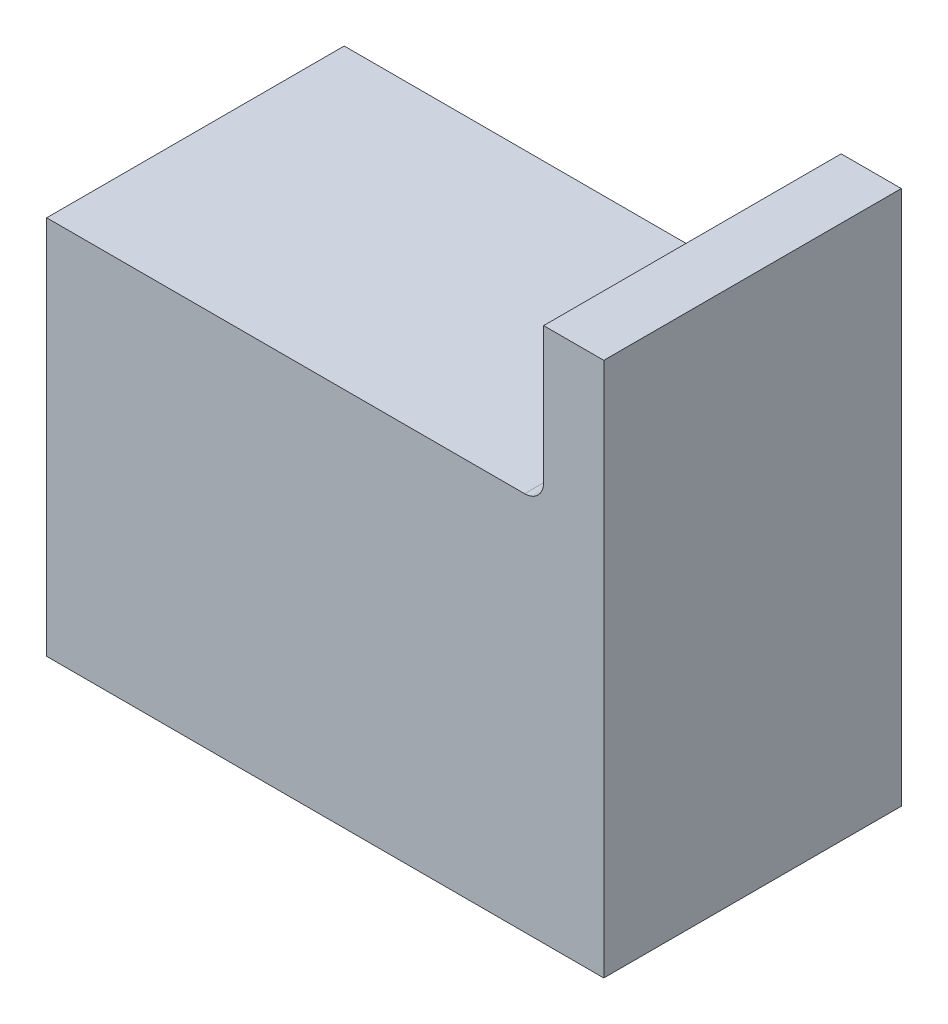
SolidWorks part; units mm, degrees
ref_plane "Front Plane" through (0, 0, 0) normal (0, 0, 1) x (1, 0, 0)
ref_plane "Top Plane" through (0, 0, 0) normal (0, 1, 0) x (1, 0, 0)
ref_plane "Right Plane" through (0, 0, 0) normal (1, 0, 0) x (0, 0, -1)
sketch "Sketch1" plane through (0, 0, 0) normal (0, 1, 0) x (1, 0, 0)
  line L1 (-44, 23.5) -> (44, 23.5)
  line L2 (-44, 23.5) -> (-44, -23.5)
  line L3 (-44, -23.5) -> (44, -23.5)
  line L4 (44, 23.5) -> (44, -23.5)
  line L5 (0, -23.5) -> (0, 23.5) construction
  line L6 (-44, 0) -> (44, 0) construction
  circle A0 centre (25.5, 18) radius 2.5
  circle A2 centre (25.5, -18) radius 2.5
  point P0 (0, 0)
  dimension "D3" = 5
  dimension "D4" = 5.5
  dimension "D1" = 47
  dimension "D2" = 88
  dimension "D5" = 18.5
extrude "Boss-Extrude1" add sketch "Sketch1" along normal blind 60
extrude "Boss-Extrude2" add sketch "Sketch1<2>" along normal blind 40 from offset 20 contours A2 | A0 region at (25.5, 0, -18) region at (25.5, 0, 18)
sketch "Sketch1<2>" plane through (0, 0, 0) normal (0, 1, 0) x (1, 0, 0) same geometry as "Sketch1"
sketch "Sketch2" plane through (0, 60, 0) normal (0, 1, 0) x (1, 0, 0)
  line L0 (0, -25.85) -> (0, 25.85) construction
  line L1 (-44, 23.5) -> (-34.5, 23.5)
  line L2 (-44, 23.5) -> (-44, -23.5)
  line L3 (-44, -23.5) -> (-34.5, -23.5)
  line L4 (-34.5, 23.5) -> (-34.5, -23.5)
  line L5 (-44, -23.5) -> (44, -23.5) construction
  line L6 (34.5, 23.5) -> (34.5, -23.5)
  line L7 (44, -23.5) -> (34.5, -23.5)
  line L8 (44, 23.5) -> (44, -23.5)
  line L9 (44, 23.5) -> (34.5, 23.5)
  dimension "D1" = 47
  dimension "D2" = 9.5
extrude "Boss-Extrude3" add sketch "Sketch2" along normal blind 24.5 contours L6 L7 L8 L9
fillet "Fillet1" radius 3 1 edges at (34.5, 60, 0)
